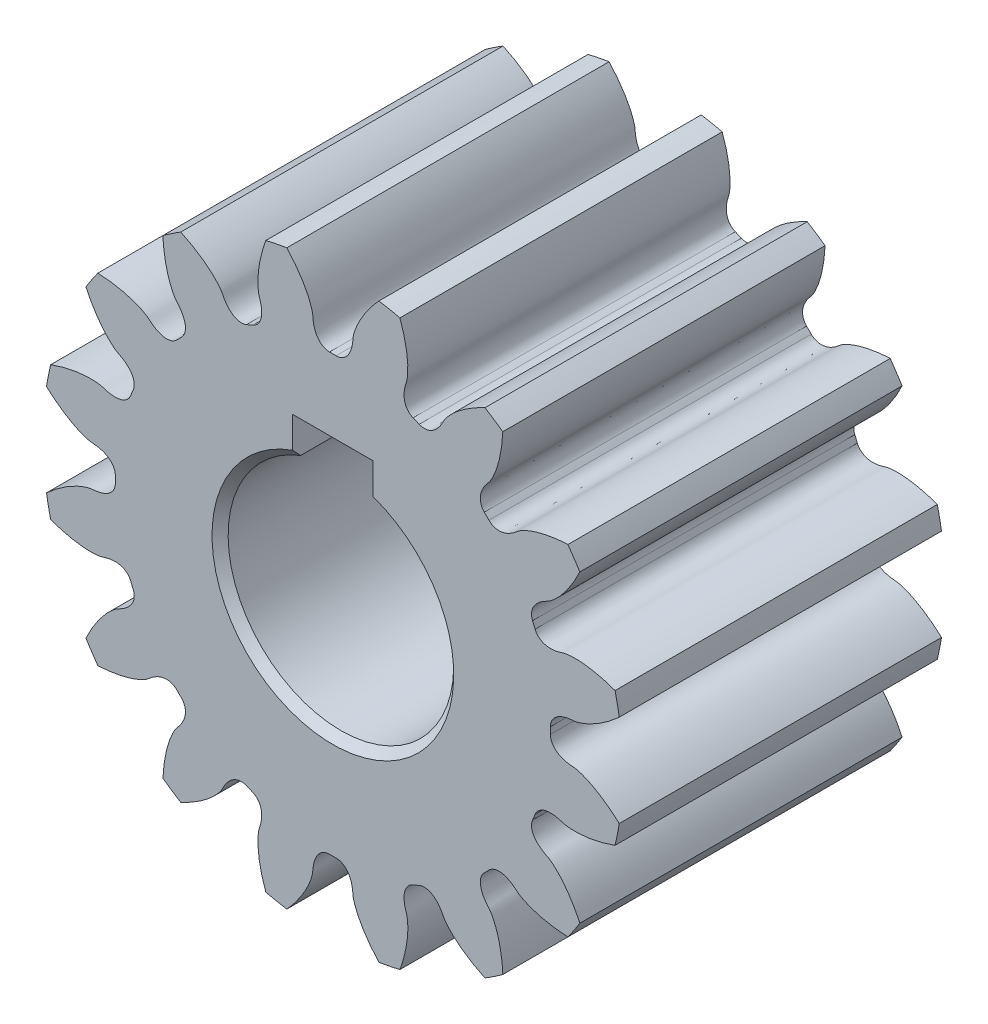
SolidWorks part; units mm, degrees
note: '?' marks a value the reader was unsure of.
ref_plane "前视基准面" through (0, 0, 0) normal (0, 0, 1) x (1, 0, 0)
ref_plane "上视基准面" through (0, 0, 0) normal (0, 1, 0) x (1, 0, 0)
ref_plane "右视基准面" through (0, 0, 0) normal (1, 0, 0) x (0, 0, -1)
ref_axis "基准轴1" through (0, 0, -88.99) along (0, 0, 1)?
sketch "Gear-BaseSketch" plane through (0, 0, 0) normal (0, 0, 1) x (1, 0, 0)
  circle A0 centre (0, 0) radius 18
  dimension "D1" = 36
extrude "2.0 模数    , 32.0000mm P.D." add sketch "Gear-BaseSketch" along normal mid plane 20
sketch "Tooth-Sketch; Backlash: 0.0000mm" plane through (0, 0, 0) normal (0, 0, 1) x (1, 0, 0)
  line L0 (0, 0) -> (0, 22.5526) construction
  arc A0 (-2.9278, 17.8489) -> (2.9278, 17.8489) centre (0, 0) cw
  arc A1 (-0.2031, 13.4985) -> (0.2031, 13.4985) centre (0, 0) cw
  spline S0 degree 3 poles (-2.9278, 17.8489) (-2.8304, 17.7422) (-2.6424, 17.5362) (-2.3874, 17.2232) (-2.1637, 16.924) (-1.9704, 16.6396) (-1.8057, 16.3724) (-1.6676, 16.1243) (-1.554, 15.897) (-1.4627, 15.6922) (-1.3916, 15.5114) (-1.3383, 15.3559) (-1.3002, 15.2269) (-1.2753, 15.1253) (-1.2481, 14.996) (-1.2453, 14.8619) (-1.2286, 14.7191) (-1.2131, 14.6143) (-1.1875, 14.4813) (-1.1462, 14.3228) (-1.0795, 14.1428) (-0.9928, 13.9741) (-0.8801, 13.8161) (-0.7315, 13.6721) (-0.5372, 13.5549) (-0.3506, 13.5052) (-0.2356, 13.5) (-0.2031, 13.4985) knots 0 0 0 0 0.08065 0.155737 0.225263 0.289226 0.347627 0.400467 0.447744 0.489459 0.525613 0.556204 0.581233 0.6007 0.614605 0.654902 0.675198 0.694889 0.714022 0.750829 0.786204 0.820996 0.856424 0.894112 0.935742 0.981856 1 1 1 1
  spline S1 degree 3 poles (2.9278, 17.8489) (2.8304, 17.7422) (2.6424, 17.5362) (2.3874, 17.2232) (2.1637, 16.924) (1.9704, 16.6396) (1.8057, 16.3724) (1.6676, 16.1243) (1.554, 15.897) (1.4627, 15.6922) (1.3916, 15.5114) (1.3383, 15.3559) (1.3002, 15.2269) (1.2753, 15.1253) (1.2481, 14.996) (1.2453, 14.8619) (1.2286, 14.7191) (1.2131, 14.6143) (1.1875, 14.4813) (1.1462, 14.3228) (1.0795, 14.1428) (0.9928, 13.9741) (0.8801, 13.8161) (0.7315, 13.6721) (0.5372, 13.5549) (0.3506, 13.5052) (0.2356, 13.5) (0.2031, 13.4985) knots 0 0 0 0 0.08065 0.155737 0.225263 0.289226 0.347627 0.400467 0.447744 0.489459 0.525613 0.556204 0.581233 0.6007 0.614605 0.654902 0.675198 0.694889 0.714022 0.750829 0.786204 0.820996 0.856424 0.894112 0.935742 0.981856 1 1 1 1
extrude "Tooth-Cut, Coarse Pitch Involute 20 deg" cut sketch "Tooth-Sketch; Backlash: 0.0000mm" against normal through all and the other way through all
pattern_circular "阵列(圆周)1" count 16 over 360 about axis through (0, 0, -88.99) along (0, 0, 1) of "Tooth-Cut, Coarse Pitch Involute 20 deg"
sketch "草图3" plane through (0, 0, 10) normal (0, 0, 1) x (1, 0, 0)
  circle A0 centre (0, 0) radius 7
  dimension "D1" = 14
extrude "切除-拉伸2" cut sketch "草图3" against normal blind 100
sketch "草图4" plane through (0, 0, -10) normal (0, 0, -1) x (-1, 0, 0)
  line L1 (-2.5, 9) -> (2.5, 9)
  line L2 (-2.5, 9) -> (-2.5, 2.2059)
  line L3 (-2.5, 2.2059) -> (2.5, 2.2059)
  line L4 (2.5, 9) -> (2.5, 2.2059)
extrude "切除-拉伸3" cut sketch "草图4" against normal through all
chamfer "倒角1" distance 0.5 angle 45 2 edges at (0, -7, 10) (0, -7, -10)
